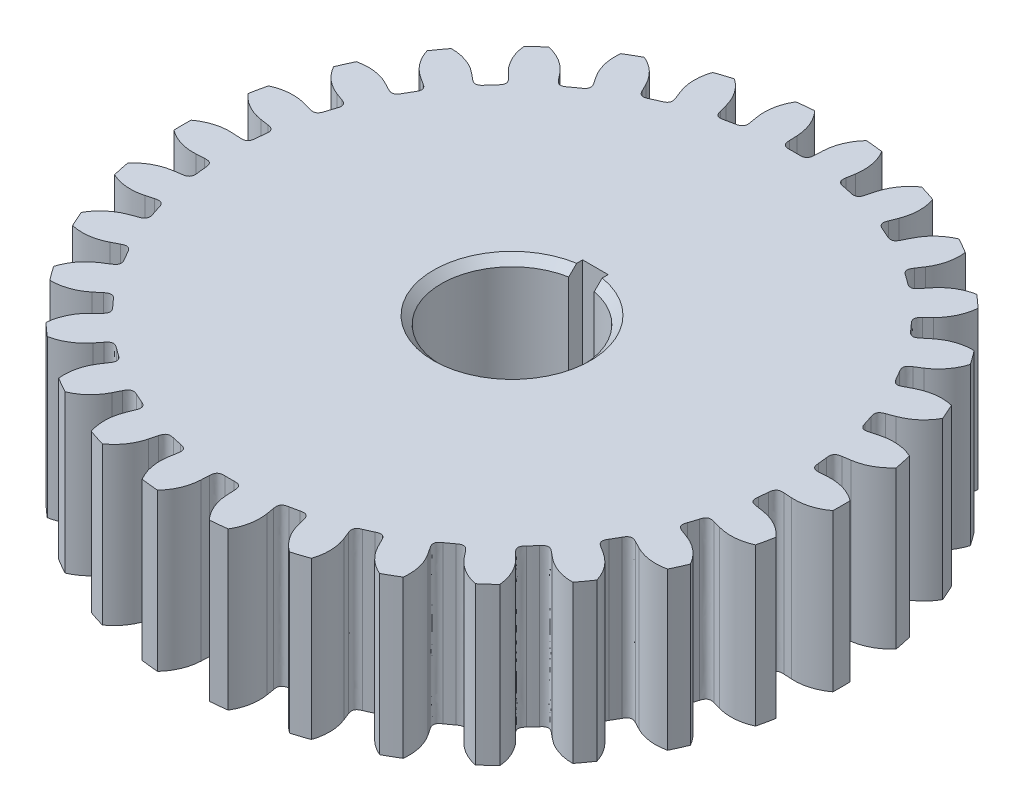
SolidWorks part; units mm, degrees
ref_plane "Front Plane" through (0, 0, 0) normal (0, 0, 1) x (1, 0, 0)
ref_plane "Top Plane" through (0, 0, 0) normal (0, 1, 0) x (1, 0, 0)
ref_plane "Right Plane" through (0, 0, 0) normal (1, 0, 0) x (0, 0, -1)
sketch "Sketch5" plane through (0, 0, 0) normal (0, 1, 0) x (1, 0, 0)
  line L0 (0, 0) -> (42, 0) construction
  line L1 (0, 0) -> (57.0983, 1.4952) construction
  line L2 (0, 0) -> (56.7694, 3.4722) construction
  line L3 (0, 0) -> (62.2852, 6.5464) construction
  line L4 (0, 0) -> (35.8028, 3.763)
  line L5 (35.9329, 2.1977) -> (37.9291, 2.3198)
  line L6 (35.9329, -2.1977) -> (37.9291, -2.3198)
  line L7 (0, 0) -> (35.8028, -3.763)
  circle A0 centre (0, 0) radius 42 construction
  circle A1 centre (0, 0) radius 36 construction
  circle A2 centre (0, 0) radius 38 construction
  arc A3 (35.8028, 3.763) -> (35.9329, 2.1977) centre (0, 0) cw
  arc A4 (37.9291, 2.3198) -> (41.9856, 1.0994) centre (38.3028, -3.7899) cw
  arc A5 (41.9856, 1.0994) -> (41.9856, -1.0994) centre (0, 0) cw
  arc A6 (37.9291, -2.3198) -> (41.9856, -1.0994) centre (38.3028, 3.7899) ccw
  arc A7 (35.8028, -3.763) -> (35.9329, -2.1977) centre (0, 0) ccw
  dimension "D1" = 84
  dimension "D5" = 72
  dimension "D6" = 76
  dimension "D2" = 1.5
  dimension "D3" = 3.5
  dimension "D4" = 6
extrude "Boss-Extrude1" add sketch "Sketch5" along normal mid plane 20
fillet "Fillet3" radius 1 2 edges at (35.9329, 0, -2.1977) (35.9329, 0, 2.1977) curvature continuous yes
pattern_circular "CirPattern3" count 30 over 360 about axis through (0, 10, 0) along (0, -1, 0) of "Fillet3", "Boss-Extrude1" reverse direction yes
sketch "Sketch6" plane through (0, 10, 0) normal (0, 1, 0) x (1, 0, 0)
  line L1 (-1.625, 10.625) -> (1.625, 10.625)
  line L2 (-1.625, 10.625) -> (-1.625, 7.375)
  line L3 (-1.625, 7.375) -> (1.625, 7.375)
  line L4 (1.625, 10.625) -> (1.625, 7.375)
  line L5 (-1.625, 10.625) -> (1.625, 7.375) construction
  line L6 (-1.625, 7.375) -> (1.625, 10.625) construction
  circle A0 centre (0, 0) radius 9
  point P3 (0, 9)
  dimension "D1" = 18
  dimension "D2" = 3.25
extrude "Cut-Extrude3" cut sketch "Sketch6" against normal through all contours L2 A0 L4 L3 | L4 A0 L2 L3 | A0 L4 L1 L2 region at (0, 10, -9.7873) region at (0, 10, -8.1635) region at (0, 10, 0.1677)
chamfer "Chamfer1" distance 1 angle 45 2 edges at (0, -10, 9) (0, 10, 9)
